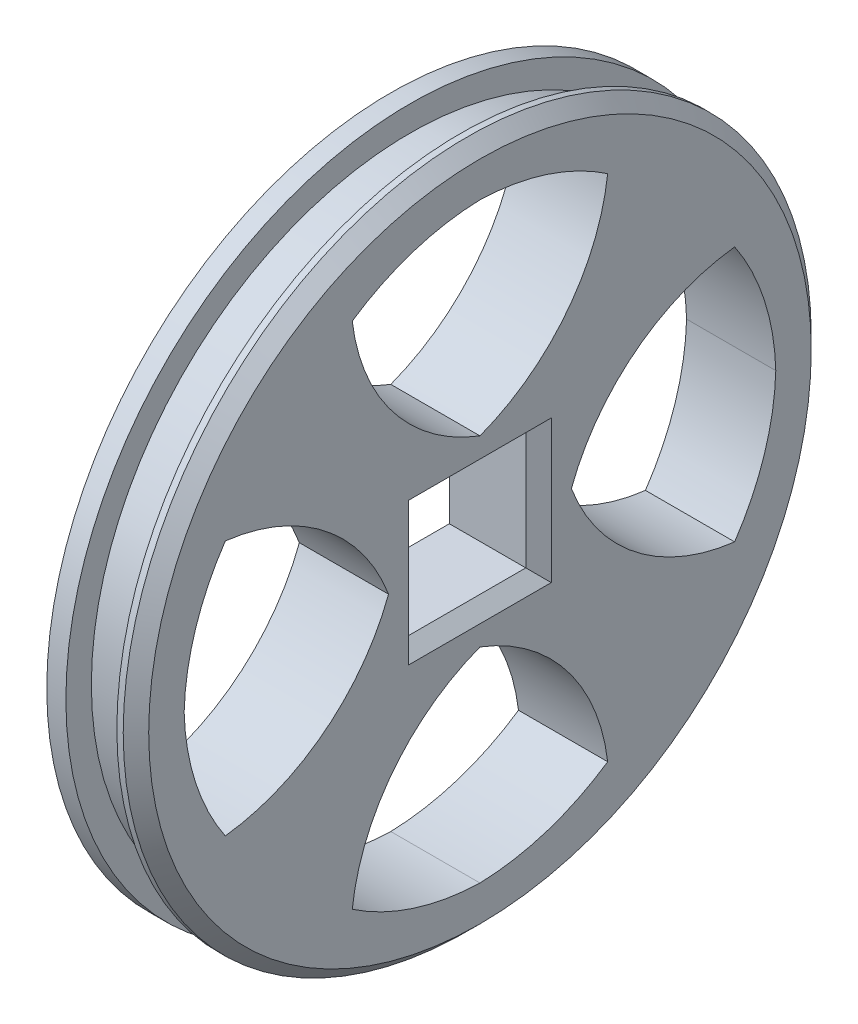
SolidWorks part; units mm, degrees
ref_plane "Front Plane" through (0, 0, 0) normal (0, 0, 1) x (1, 0, 0)
ref_plane "Top Plane" through (0, 0, 0) normal (0, 1, 0) x (1, 0, 0)
ref_plane "Right Plane" through (0, 0, 0) normal (1, 0, 0) x (0, 0, -1)
sketch "Sketch1" plane through (0, 0, 0) normal (1, 0, 0) x (0, 0, -1)
  circle A0 centre (0, 0) radius 13.5
  circle A1 centre (0, 0) radius 3.1168 construction
  dimension "D1" = 27
extrude "Boss-Extrude1" add sketch "Sketch1" along normal mid plane 3.5
sketch "Sketch2" plane through (0, 0, 0) normal (1, 0, 0) x (0, 0, -1)
  line L0 (0, 0) -> (0, 14.8201) construction
  arc A0 (0, 3.5875) -> (-5.0122, 9.994) centre (2.7702, 10.9187) cw
  arc A1 (-5.0122, 9.994) -> (0, 11.6087) centre (0.2591, 2.218) cw
  arc A2 (5.0122, 9.994) -> (0, 11.6087) centre (-0.2591, 2.218) ccw
  arc A3 (0, 3.5875) -> (5.0122, 9.994) centre (-2.7702, 10.9187) ccw
extrude "Cut-Extrude1" cut sketch "Sketch2" along normal through all both and the other way through all
pattern_circular "CirPattern1" count 4 over 360 about axis through (1.75, 0, 0) along (-1, 0, 0) of "Cut-Extrude1" reverse direction yes
sketch "Sketch3" plane through (0, 0, 0) normal (1, 0, 0) x (0, 0, -1)
  line L1 (2.2981, -2.2981) -> (-2.2981, -2.2981)
  line L2 (2.2981, -2.2981) -> (2.2981, 2.2981)
  line L3 (2.2981, 2.2981) -> (-2.2981, 2.2981)
  line L4 (-2.2981, -2.2981) -> (-2.2981, 2.2981)
  line L5 (2.2981, -2.2981) -> (-2.2981, 2.2981) construction
  line L6 (2.2981, 2.2981) -> (-2.2981, -2.2981) construction
  circle A0 centre (0, 0) radius 3.25 construction
  dimension "D1" = 6.5
extrude "Cut-Extrude2" cut sketch "Sketch3" along normal through all both and the other way through all
chamfer "Chamfer1" distance 0.5 angle 45 5 edges at (1.75, 0, 2.2981) (1.75, -2.2981, 0) (1.75, 2.2981, 0) (1.75, 0, -2.2981) (1.75, 0, -13.5)
sketch "Sketch4" plane through (0, 0, 0) normal (1, 0, 0) x (0, 0, -1)
  circle A0 centre (0, 0) radius 13.5
  circle A1 centre (0, 0) radius 12.5
  circle A2 centre (0, 0) radius 13.5 construction
  dimension "D1" = 1
extrude "Cut-Extrude3" cut sketch "Sketch4" against normal mid plane 2
equation "\"axis_diameter\"=5.66"
equation "\"padding\"=0.5"
